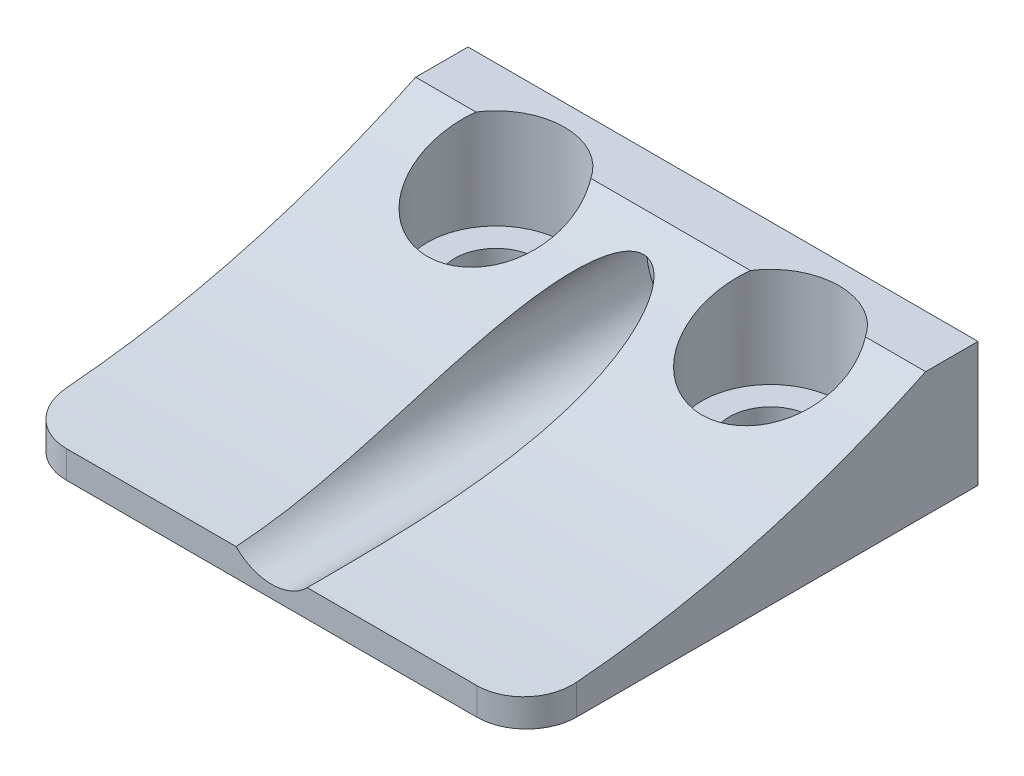
SolidWorks part; units mm, degrees
ref_plane "Front Plane" through (0, 0, 0) normal (0, 0, 1) x (1, 0, 0)
ref_plane "Top Plane" through (0, 0, 0) normal (0, 1, 0) x (1, 0, 0)
ref_plane "Right Plane" through (0, 0, 0) normal (1, 0, 0) x (0, 0, -1)
sketch "Sketch1" plane through (0, 0, 0) normal (0, 1, 0) x (1, 0, 0)
  line L1 (-10.225, -9.05) -> (10.225, -9.05)
  line L2 (-10.225, -9.05) -> (-10.225, 9.05)
  line L3 (-10.225, 9.05) -> (10.225, 9.05)
  line L4 (10.225, -9.05) -> (10.225, 9.05)
  line L5 (-10.225, -9.05) -> (10.225, 9.05) construction
  line L6 (-10.225, 9.05) -> (10.225, -9.05) construction
  point P0 (0, 0)
  dimension "D1" = 20.45
  dimension "D2" = 18.1
extrude "Boss-Extrude2" add sketch "Sketch1" along normal blind 1
sketch "Sketch3" plane through (0, 0, 0) normal (1, 0, 0) x (0, 0, -1)
  line L0 (9.05, 1) -> (9.05, 5)
  line L1 (9.05, 1) -> (3.05, 1)
  line L3 (9.05, 5) -> (7.05, 5)
  line L4 (-9.05, 1) -> (9.05, 1) construction
  line L5 (3.05, 1) -> (7.05, 5)
  dimension "D1" = 6
  dimension "D2" = 4
  dimension "D3" = 2
extrude "Boss-Extrude3" add sketch "Sketch3" along normal up to surface and the other way up to surface up to face at (10.225, 0.5, 0) other way up to face at (-10.225, 0.5, 0)
ref_plane "Plane5" through (0, 5, 0) normal (0, 1, 0) x (1, 0, 0)
sketch "Sketch4" plane through (0, 5, 0) normal (0, 1, 0) x (1, 0, 0)
  line L0 (-10.225, 3.05) -> (-10.225, 7.05) construction
  line L1 (10.225, 9.05) -> (-10.225, 9.05) construction
  line L2 (10.225, 3.05) -> (10.225, 7.05) construction
  circle A0 centre (-5.505, 5.45) radius 1.65
  circle A1 centre (5.505, 5.45) radius 1.65
  dimension "D5" = 3.3
  dimension "D6" = 3.3
  dimension "D1" = 4.72
  dimension "D2" = 3.6
  dimension "D3" = 3.6
  dimension "D4" = 4.72
extrude "Cut-Extrude1" cut sketch "Sketch4" against normal up to surface (5 mm away) up to face at (0, 0, 0)
sketch "Sketch10" plane through (0, 0, 0) normal (1, 0, 0) x (0, 0, -1)
  line L0 (7.05, 5) -> (6.95, 5)
  line L1 (-9.05, 1) -> (-9.05, 1.1)
  line L6 (-9.05, 0) -> (9.05, 0)
  line L7 (9.05, 0) -> (9.05, 5)
  line L8 (9.05, 5) -> (7.05, 5)
  line L9 (7.05, 5) -> (3.05, 1)
  line L10 (3.05, 1) -> (-9.05, 1)
  line L11 (-9.05, 1) -> (-9.05, 0)
  line L12 (-9.05, 0) -> (9.05, 0)
  line L13 (9.05, 0) -> (9.05, 5)
  line L14 (9.05, 5) -> (7.05, 5)
  line L15 (7.05, 5) -> (3.05, 1)
  line L16 (3.05, 1) -> (-9.05, 1)
  line L17 (-9.05, 1) -> (-9.05, 0)
  circle A0 centre (-10.3198, 41.0798) radius 40
  dimension "D1" = 80
  dimension "D3" = 0.1
  dimension "D4" = 0.1
  dimension "D2" = 0
extrude "Boss-Extrude5" add sketch "Sketch10" along normal up to surface (10.225 mm away) and the other way up to surface (10.225 mm away) contours L16 L15 L0 A0 L1 region at (0, 2.1228, -0.9483) up to face at (10.225, 2, -1.6833) other way up to face at (-10.225, 2, -1.6833)
sketch "Sketch6" plane through (0, 5, 0) normal (0, 1, 0) x (1, 0, 0)
  circle A0 centre (-5.505, 5.45) radius 2.75
  circle A1 centre (5.505, 5.45) radius 2.75
  dimension "D1" = 5.5
  dimension "D2" = 5.5
extrude "Cut-Extrude2" cut sketch "Sketch6" against normal blind 4
sketch "Sketch7" plane through (0, 0, 0) normal (0, 0, 1) x (1, 0, 0)
  line L0 (3.2684, 5) -> (-3.2684, 5) construction
  line L1 (-10.225, 1) -> (-10.225, 5) construction
  circle A0 centre (0, 2.5) radius 1.15
  dimension "D3" = 2.3
  dimension "D1" = 2.5
  dimension "D2" = 10.225
extrude "Cut-Extrude3" cut sketch "Sketch7" against normal up to surface (9.05 mm away) up to face at (0, 2.5, -9.05)
sketch "Sketch8" plane through (0, 0, 0) normal (0, 0, 1) x (1, 0, 0)
  circle A0 centre (0, 2.5) radius 2
  dimension "D1" = 4
extrude "Cut-Extrude4" cut sketch "Sketch8" against normal blind 8 and the other way up to surface (9.05 mm away) other way up to face at (0, 0.55, 9.05)
fillet "Fillet1" radius 2 2 edges at (-10.225, 0.55, 9.05) (10.225, 0.55, 9.05)
